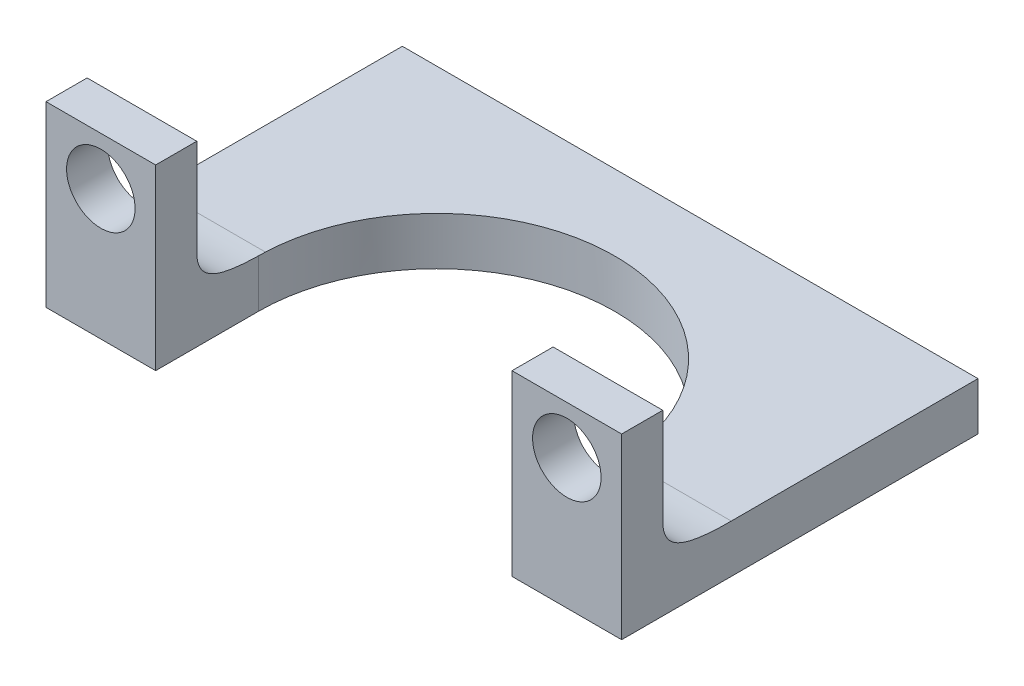
SolidWorks part; units mm, degrees
ref_plane "Plano frontal" through (0, 0, 0) normal (0, 0, 1) x (1, 0, 0)
ref_plane "Plano superior" through (0, 0, 0) normal (0, 1, 0) x (1, 0, 0)
ref_plane "Plano direito" through (0, 0, 0) normal (1, 0, 0) x (0, 0, -1)
sketch "Esboço1" plane through (0, 0, 0) normal (0, 1, 0) x (1, 0, 0)
  line L1 (-21, 13) -> (21, 13)
  line L2 (-21, 13) -> (-21, -13)
  line L3 (-21, -13) -> (21, -13)
  line L4 (21, 13) -> (21, -13)
  line L5 (-21, 13) -> (21, -13) construction
  line L6 (-21, -13) -> (21, 13) construction
  point P0 (0, 0)
  dimension "D1" = 26
  dimension "D2" = 42
extrude "Ressalto-extrusão1" add sketch "Esboço1" along normal blind 3.5
sketch "Esboço2" plane through (0, 3.5, 0) normal (0, 1, 0) x (1, 0, 0)
  line L0 (-21, 13) -> (-21, -13) construction
  line L1 (-21, -10) -> (21, -10)
  line L2 (-21, -10) -> (-21, -13)
  line L3 (-21, -13) -> (21, -13)
  line L4 (21, -10) -> (21, -13)
  line L5 (21, -13) -> (21, 13) construction
  line L6 (-21, -13) -> (21, -13) construction
  dimension "D1" = 3
extrude "Ressalto-extrusão2" add sketch "Esboço2" along normal blind 9.5
sketch "Esboço3" plane through (0, 0, 0) normal (0, -1, 0) x (1, 0, 0)
  line L0 (-21, 13) -> (21, 13) construction
  line L1 (13, 5.5) -> (13, 13)
  line L2 (13, 13) -> (-13, 13)
  line L3 (-13, 13) -> (-13, 5.5)
  circle A0 centre (0, 5.5) radius 13
  line M2 (21, 13) -> (-21, 13)
  dimension "D1" = 7.5
extrude "Corte-extrusão1" cut sketch "Esboço3" against normal up to surface (13 mm away) contours A0 L2 | A0 L3 M2 | A0 L1 M2 region at (12.2983, 0, 11.1611) region at (0, 0, 3.7225) region at (-12.2983, 0, 11.1611) up to face at (0, 13, 11.5)
sketch "Esboço5" plane through (0, 0, 10) normal (0, 0, -1) x (-1, 0, 0)
  line L0 (13, 13) -> (21, 13) construction
  circle A0 centre (17, 9.5) radius 2.5
  dimension "D1" = 3.5
  dimension "D2" = 4
extrude "Corte-extrusão2" cut sketch "Esboço5" against normal up to surface (3 mm away) up to face at (-17, 6.5, 13)
sketch "Esboço6" plane through (0, 0, 10) normal (0, 0, -1) x (-1, 0, 0)
  line L0 (-13, 3.5) -> (-13, 13) construction
  line L1 (-21, 13) -> (-13, 13) construction
  circle A0 centre (-17, 9.5) radius 2.5
  dimension "D1" = 4
  dimension "D2" = 3.5
extrude "Corte-extrusão3" cut sketch "Esboço6" against normal up to surface (3 mm away) up to face at (17, 6.5, 13)
fillet "Filete1" radius 5 2 edges second distance 2.5 first distance on face at (1, 3.5, 1.5)
